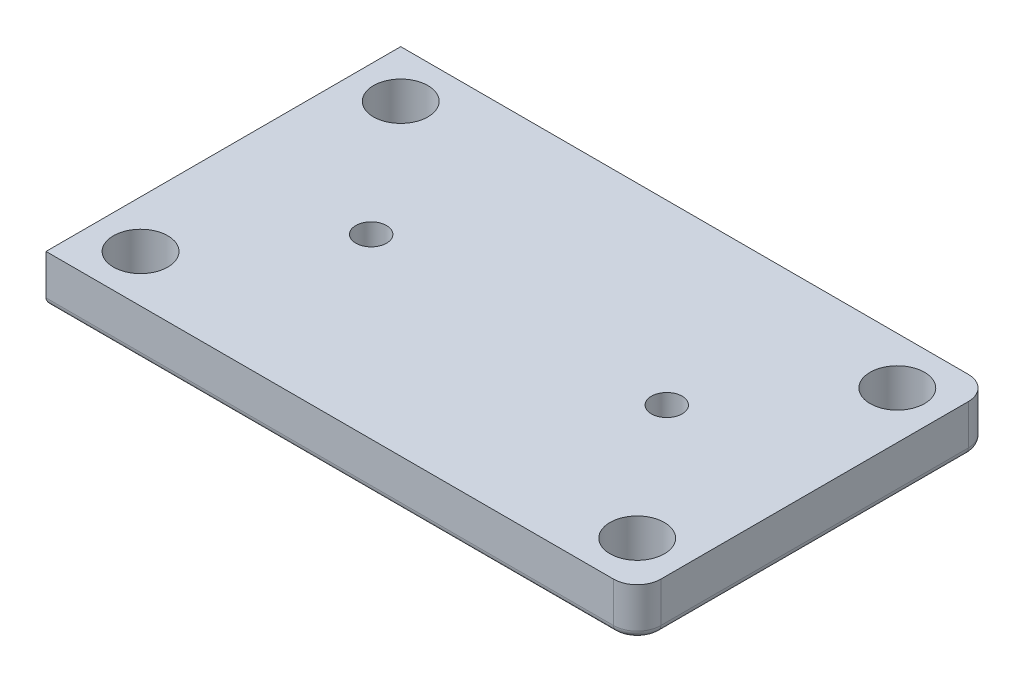
SolidWorks part; units mm, degrees
ref_plane "Front Plane" through (0, 0, 0) normal (0, 0, 1) x (1, 0, 0)
ref_plane "Top Plane" through (0, 0, 0) normal (0, 1, 0) x (1, 0, 0)
ref_plane "Right Plane" through (0, 0, 0) normal (1, 0, 0) x (0, 0, -1)
sketch "Sketch3" plane through (0, 0, 0) normal (0, 1, 0) x (1, 0, 0)
  line L0 (0, 0) -> (12.5, 0) construction
  line L1 (-12.5, -7.5) -> (12.5, -7.5)
  line L2 (-12.5, -7.5) -> (-12.5, 7.5)
  line L3 (-12.5, 7.5) -> (12.5, 7.5)
  line L4 (12.5, -7.5) -> (12.5, 7.5)
  line L5 (-12.5, -7.5) -> (12.5, 7.5) construction
  line L6 (-12.5, 7.5) -> (12.5, -7.5) construction
  line L7 (0, 0) -> (0, -4.3969) construction
  circle A0 centre (6.25, 0) radius 0.65
  circle A1 centre (-6.25, 0) radius 0.65
  point P0 (0, 0)
  dimension "D3" = 1.3
  dimension "D1" = 25
  dimension "D2" = 15
extrude "Boss-Extrude5" add sketch "Sketch3" along normal blind 2
sketch "Sketch6" plane through (0, 2, 0) normal (0, 1, 0) x (1, 0, 0)
  line L0 (-10.5, 5.5) -> (-10.5, -5.5)
  line L1 (-12.5, 7.5) -> (12.5, 7.5)
  line L2 (-12.5, 7.5) -> (-12.5, -7.5)
  line L3 (-12.5, -7.5) -> (12.5, -7.5)
  line L4 (12.5, 7.5) -> (12.5, -7.5)
  line L5 (-10.5, -5.5) -> (10.5, -5.5)
  line L6 (10.5, 5.5) -> (10.5, -5.5)
  line L7 (-10.5, 5.5) -> (10.5, 5.5)
  line L8 (0, 0) -> (0, 9.2986) construction
  line L9 (-0.1913, 0) -> (14.3497, 0) construction
  circle A0 centre (-10.5, 5.5) radius 1.15
  circle A1 centre (10.5, 5.5) radius 1.15
  circle A2 centre (10.5, -5.5) radius 1.15
  circle A3 centre (-10.5, -5.5) radius 1.15
  dimension "D2" = 2.3
  dimension "D1" = 2
extrude "Cut-Extrude1" cut sketch "Sketch6" against normal blind 2 contours L7 A0 L0 | L0 A0 L7 | A1 L7 L6 | A1 L6 L7 | L5 A2 L6 | L6 A2 L5 | A3 L5 L0 | A3 L0 L5 region at (-10.0119, 2, -5.0119) region at (-10.6627, 2, -5.6627) region at (-10.0119, 2, 5.0119) region at (-10.6627, 2, 5.6627) region at (10.6627, 2, -5.6627) region at (10.0119, 2, -5.0119) region at (10.0119, 2, 5.0119) region at (10.6627, 2, 5.6627)
fillet "Fillet1" radius 0.3 4 edges at (12.5, 0, 0) (0, 0, -7.5) (-12.5, 0, 0) (0, 0, 7.5)
fillet "Fillet2" radius 1 4 edges at (12.4121, 0.0879, 7.4121) (12.4121, 0.0879, -7.4121) (12.5, 1.15, -7.5) (12.5, 1.15, 7.5)
